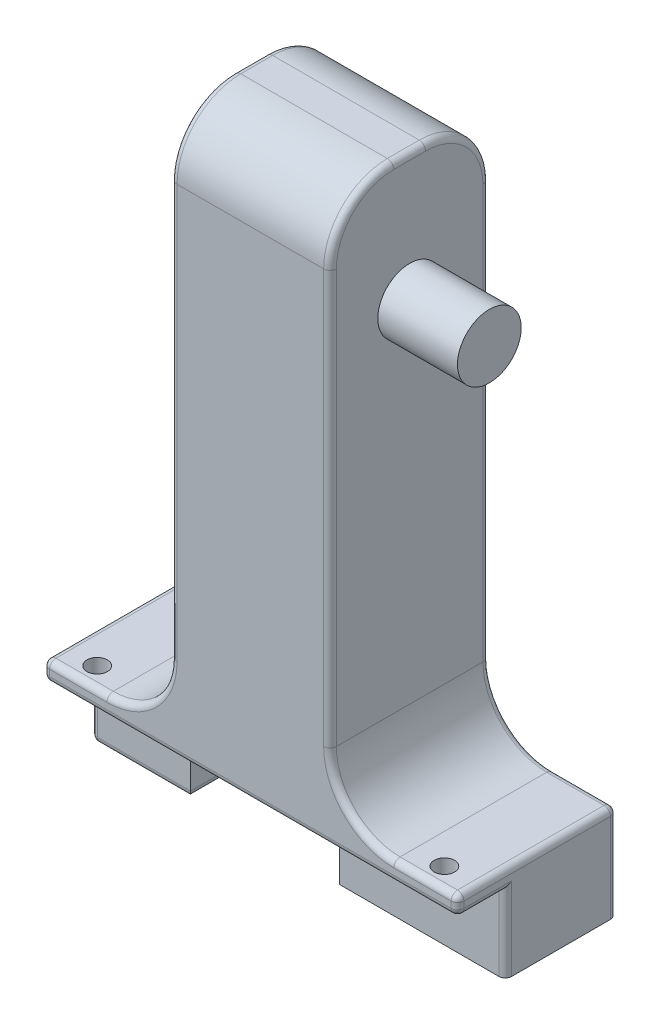
SolidWorks part; units mm, degrees
ref_plane "Front Plane" through (0, 0, 0) normal (0, 0, 1) x (1, 0, 0)
ref_plane "Top Plane" through (0, 0, 0) normal (0, 1, 0) x (1, 0, 0)
ref_plane "Right Plane" through (0, 0, 0) normal (1, 0, 0) x (0, 0, -1)
sketch "Sketch2" plane through (0, 0, 0) normal (0, 1, 0) x (1, 0, 0)
  line L1 (-32.5, -12.5) -> (32.5, -12.5)
  line L2 (-32.5, -12.5) -> (-32.5, 12.5)
  line L3 (-32.5, 12.5) -> (32.5, 12.5)
  line L4 (32.5, -12.5) -> (32.5, 12.5)
  line L5 (-32.5, -12.5) -> (32.5, 12.5) construction
  line L6 (-32.5, 12.5) -> (32.5, -12.5) construction
  point P0 (0, 0)
  dimension "D1" = 65
  dimension "D2" = 25
extrude "Boss-Extrude1" add sketch "Sketch2" along normal blind 3
sketch "Sketch3" plane through (0, 0, 0) normal (0, -1, 0) x (1, 0, 0)
  line L0 (32.5, -12.5) -> (-32.5, -12.5) construction
  line L1 (-32.5, 5) -> (-16.9, 5)
  line L2 (-32.5, 5) -> (-32.5, -12.5)
  line L3 (-32.5, -12.5) -> (-16.9, -12.5)
  line L4 (-16.9, 5) -> (-16.9, -12.5)
  line L10 (32.5, 5) -> (6.5, 5)
  line L12 (6.5, 5) -> (6.5, 0)
  line L13 (6.5, 0) -> (12.5, 0)
  line L14 (12.5, 0) -> (12.5, -12.5)
  line L15 (32.5, -12.5) -> (-32.5, -12.5) construction
  line L16 (12.5, -12.5) -> (32.5, -12.5)
  line L17 (32.5, -12.5) -> (32.5, 5)
  line L18 (-32.5, -12.5) -> (-32.5, 12.5) construction
  point P16 (0, 0)
  dimension "D1" = 15.6
  dimension "D2" = 26
  dimension "D3" = 20
  dimension "D4" = 17.5
extrude "Boss-Extrude2" add sketch "Sketch3" along normal blind 12
sketch "Sketch5" plane through (0, 3, 0) normal (0, 1, 0) x (1, 0, 0)
  circle A0 centre (27.2349, -9.2897) radius 1.6
  circle A1 centre (-27.2349, -9.2897) radius 1.6
  circle A2 centre (27.2349, -9.2897) radius 1.6 construction
extrude "Cut-Extrude1" cut sketch "Sketch5" against normal through all
sketch "Sketch6" plane through (0, 3, 0) normal (0, 1, 0) x (1, 0, 0)
  line L0 (-32.5, -12.5) -> (32.5, -12.5) construction
  line L1 (12.5, -12.5) -> (-12.5, -12.5)
  line L2 (12.5, -12.5) -> (12.5, 12.5)
  line L3 (12.5, 12.5) -> (-12.5, 12.5)
  line L4 (-12.5, -12.5) -> (-12.5, 12.5)
  line L5 (32.5, 12.5) -> (-32.5, 12.5) construction
  line L6 (0, -20.7065) -> (0, 20.7065) construction
  point P12 (0, 0)
  dimension "D1" = 25
extrude "Boss-Extrude3" add sketch "Sketch6" along normal blind 84.9
sketch "Sketch7" plane through (12.5, 0, 0) normal (1, 0, 0) x (0, 0, -1)
  line L0 (12.5, 87.9) -> (12.5, 3) construction
  line L2 (-12.5, 87.9) -> (-12.5, 3) construction
  line L3 (-12.5, 87.9) -> (12.5, 87.9) construction
  circle A0 centre (0, 67.9) radius 12.5
  dimension "D1" = 20
sketch "Sketch9" plane through (12.5, 0, 0) normal (1, 0, 0) x (0, 0, -1)
  circle A0 centre (0, 67.9) radius 5
  dimension "D1" = 10
extrude "Boss-Extrude4" add sketch "Sketch9" along normal blind 12.5
sketch "Sketch8" plane through (-12.5, 0, 0) normal (-1, 0, 0) x (0, 0, 1)
  line L0 (12.5, 87.9) -> (12.5, 3) construction
  line L1 (-12.5, 87.9) -> (-12.5, 3) construction
  circle A1 centre (0, 67.9) radius 12.5
ref_axis "Axis1" through (-18.9714, 67.9, 0) along (1, 0, 0)
sketch "Sketch10" plane through (-12.5, 0, 0) normal (-1, 0, 0) x (0, 0, 1)
  line L0 (-3.75, 72.2589) -> (-3.75, 78.7589)
  line L1 (3.75, 72.2589) -> (3.75, 78.7589)
  line L2 (-3.75, 63.5411) -> (-3.75, 57.0411)
  line L3 (3.75, 63.5411) -> (3.75, 57.0411)
  line L4 (0, 37.8885) -> (0, 97.9115) construction
  line L5 (-3.75, 78.7589) -> (-2.4534, 85.3804)
  line L6 (3.75, 78.7589) -> (2.4534, 85.3804)
  line L7 (-27.0629, 67.9) -> (27.0629, 67.9) construction
  line L8 (3.75, 57.0411) -> (2.4534, 50.4196)
  line L9 (-3.75, 57.0411) -> (-2.4534, 50.4196)
  arc A0 (-3.75, 72.2589) -> (-3.75, 63.5411) centre (0, 67.9) ccw
  arc A1 (2.4534, 85.3804) -> (-2.4534, 85.3804) centre (0, 84.9) ccw
  arc A2 (2.4534, 50.4196) -> (-2.4534, 50.4196) centre (0, 50.9) cw
  arc A3 (3.75, 63.5411) -> (3.75, 72.2589) centre (0, 67.9) ccw
  point P15 (0, 67.9)
  point P22 (0, 67.9)
  dimension "D1" = 11.5
  dimension "D4" = 5
  dimension "D2" = 7.5
  dimension "D3" = 6.5
  dimension "D5" = 17
extrude "Cut-Extrude2" cut sketch "Sketch10" against normal blind 3
sketch "Sketch11" plane through (-9.5, 0, 0) normal (-1, 0, 0) x (0, 0, 1)
  circle A0 centre (0, 67.9) radius 5.75
  arc A1 (3.75, 63.5411) -> (3.75, 72.2589) centre (0, 67.9) ccw construction
extrude "Cut-Extrude3" cut sketch "Sketch11" against normal blind 1
fillet "Fillet1" radius 10 4 edges at (0, 87.9, 12.5) (0, 87.9, -12.5) (-12.5, 3, 0) (12.5, 3, 0)
fillet "Fillet2" radius 1 33 edges at (27.5, 3, 12.5) (15.4289, 5.9289, 12.5) (12.5, 45.45, 12.5) (12.5, 84.9711, 9.5711) (12.5, 87.9, 0) (12.5, 84.9711, -9.5711) (12.5, 45.45, -12.5) (15.4289, 5.9289, -12.5) (-27.5, 3, 12.5) (-15.4289, 5.9289, 12.5) (-12.5, 45.45, 12.5) (-12.5, 84.9711, 9.5711) (-12.5, 87.9, 0) (-12.5, 84.9711, -9.5711) (-27.5, 3, -12.5) (-15.4289, 5.9289, -12.5) (-24.7, -12, 5) (-16.9, -12, -3.75) (-24.7, -12, -12.5) (-32.5, -12, -3.75) (-32.5, 1.5, 12.5) (-32.5, -6, 5) (-32.5, 0, 8.75) (32.5, 1.5, 12.5) (32.5, -6, 5) (32.5, 0, 8.75) (0, 0, 12.5) (-32.5, -4.5, -12.5) (-32.5, 3, 0) (32.5, 3, 0) (32.5, -4.5, -12.5) (27.5, 3, -12.5) (-12.5, 45.45, -12.5)
